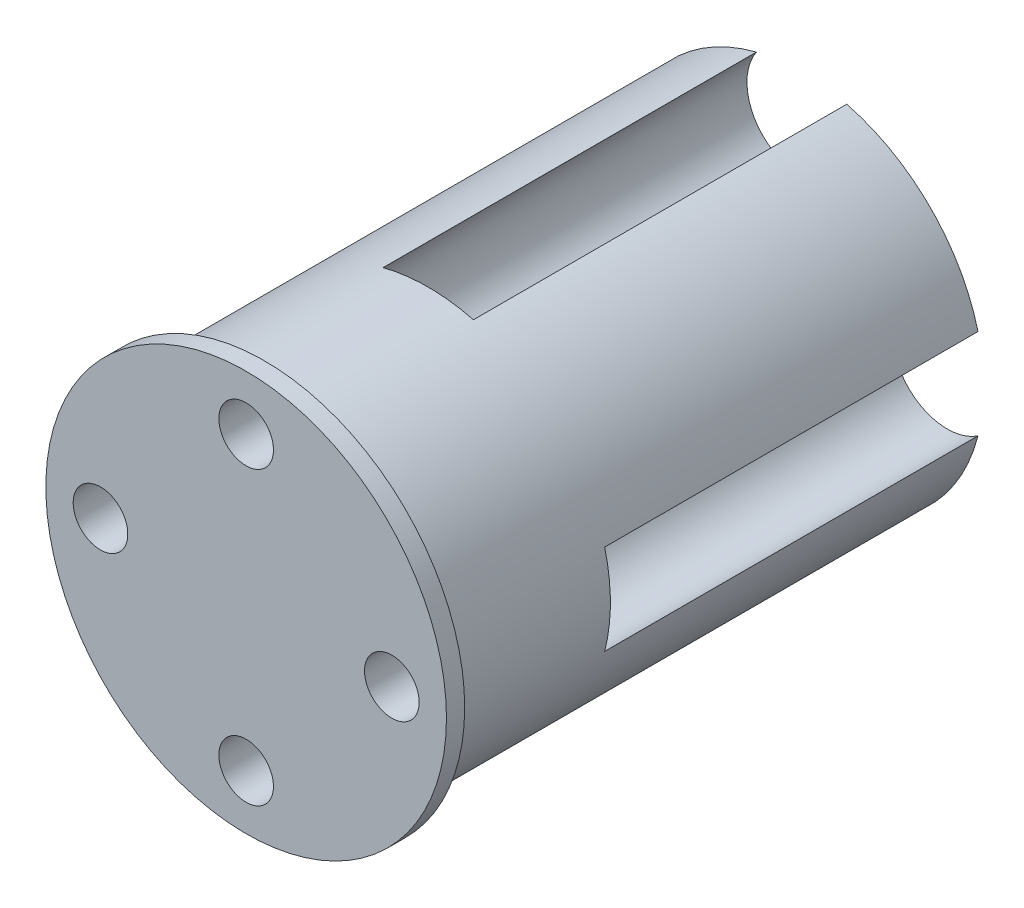
SolidWorks part; units mm, degrees
ref_plane "Ebene vorne" through (0, 0, 0) normal (0, 0, 1) x (1, 0, 0)
ref_plane "Ebene oben" through (0, 0, 0) normal (0, 1, 0) x (1, 0, 0)
ref_plane "Ebene rechts" through (0, 0, 0) normal (1, 0, 0) x (0, 0, -1)
sketch "Skizze1" plane through (0, 0, 0) normal (0, 0, 1) x (1, 0, 0)
  circle A0 centre (0, 0) radius 10
  circle A1 centre (0, 0) radius 8
  circle A2 centre (8, 0) radius 1.5
  circle A3 centre (0, 0) radius 9.5
  circle A4 centre (0, -8) radius 1.5
  circle A5 centre (-8, 0) radius 1.5
  circle A6 centre (0, 8) radius 1.5
  point P16 (0, 0)
  dimension "D1" = 20
  dimension "D2" = 19
  dimension "D3" = 3
  dimension "D4" = 4
extrude "Aufsatz-Linear austragen1" add sketch "Skizze1" along normal blind 30.5 contours A0 A3 | A6 A3 A5 A1 | A5 A3 A4 A1 | A4 A3 A2 A1 | A6 A1 A2 A3 | A6 A1 A5 A4 A2 region at (-9.7172, 0, 0) region at (0, 0, 0) region at (5.7904, 5.7904, 0) region at (5.7904, -5.7904, 0) region at (-5.7904, 5.7904, 0) region at (-5.7904, -5.7904, 0)
sketch "Skizze2" plane through (0, 0, 0) normal (0, 0, -1) x (-1, 0, 0)
  circle A0 centre (0, 8) radius 3
  circle A1 centre (8, 0) radius 3
  circle A2 centre (0, -8) radius 3
  circle A3 centre (-8, 0) radius 3
  point P12 (0, 0)
  dimension "D1" = 6
  dimension "D2" = 4
extrude "Schnitt-Linear austragen1" cut sketch "Skizze2" against normal offset from surface (20.5 mm away) 10 up to face at (9.5, 0, 30.5)
sketch "Skizze3" plane through (0, 0, 0) normal (0, 0, -1) x (-1, 0, 0)
  line L0 (0, 0) -> (-5.6569, 5.6569) construction
  circle A0 centre (0, 0) radius 8
  circle A1 centre (-5.6569, 5.6569) radius 1.25
  circle A2 centre (5.6569, 5.6569) radius 1.25
  circle A3 centre (5.6569, -5.6569) radius 1.25
  circle A4 centre (-5.6569, -5.6569) radius 1.25
  point P15 (0, 0)
  dimension "D1" = 4
extrude "Schnitt-Linear austragen2" cut sketch "Skizze3" against normal blind 16 contours A0 A1 | L0 A1 A0 | A1 L0 A0 | A0 A2 | A0 A2 | A0 A3 | A0 A3 | A0 A4 | A0 A4 region at (5.6348, 4.9043, 0) region at (4.9043, 5.6348, 0) region at (6.0193, 6.0193, 0) region at (5.2696, -5.2696, 0) region at (6.0193, -6.0193, 0) region at (-6.0193, 6.0193, 0) region at (-5.2696, 5.2696, 0) region at (-5.2696, -5.2696, 0) region at (-6.0193, -6.0193, 0)
sketch "Skizze4" plane through (0, 0, 30.5) normal (0, 0, 1) x (1, 0, 0)
  circle A0 centre (0, 0) radius 11
  circle A1 centre (8, 0) radius 1.5
  circle A2 centre (0, 8) radius 1.5
  circle A3 centre (0, -8) radius 1.5
  circle A4 centre (-8, 0) radius 1.5
  dimension "D1" = 22
extrude "Aufsatz-Linear austragen2" add sketch "Skizze4" against normal blind 1
